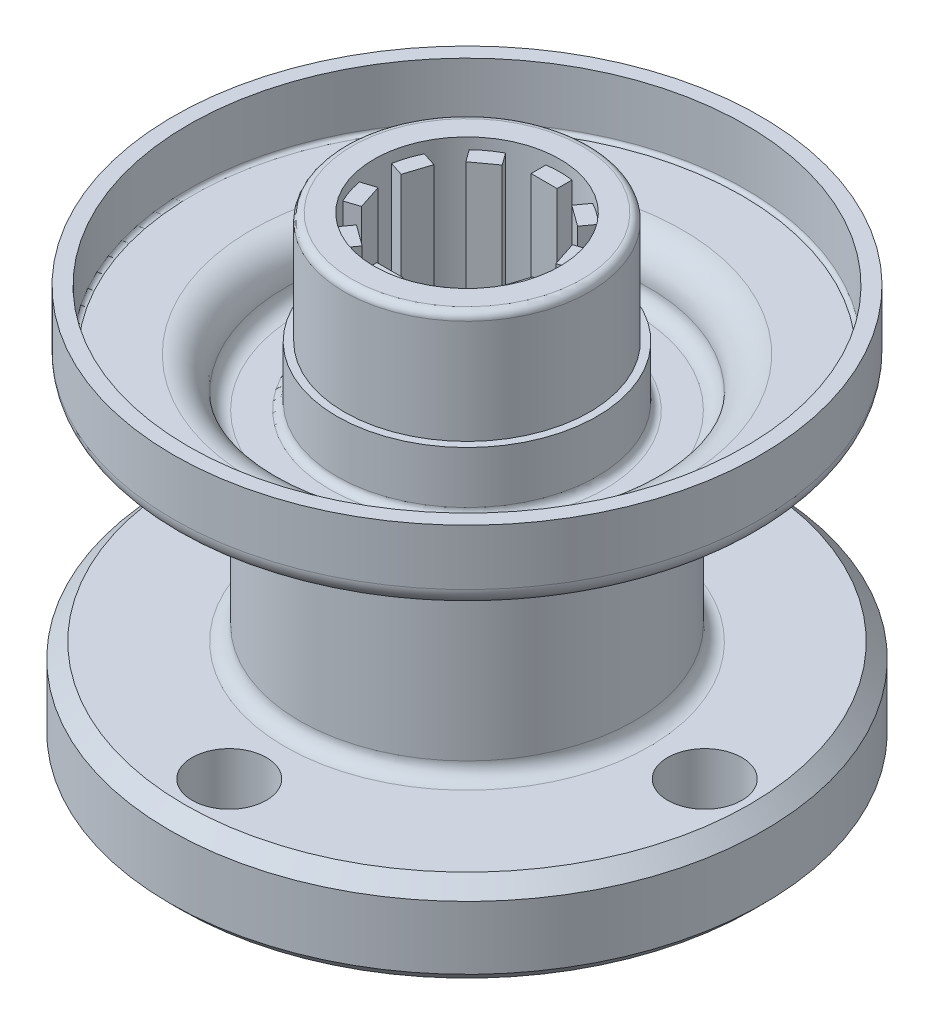
SolidWorks part; units mm, degrees
ref_plane "Front Plane" through (0, 0, 0) normal (0, 0, 1) x (1, 0, 0)
ref_plane "Top Plane" through (0, 0, 0) normal (0, 1, 0) x (1, 0, 0)
ref_plane "Right Plane" through (0, 0, 0) normal (1, 0, 0) x (0, 0, -1)
sketch "Sketch1" plane through (0, 0, 0) normal (0, 1, 0) x (1, 0, 0)
  circle A0 centre (0, 0) radius 40
  dimension "D1" = 80
extrude "Extrude1" add sketch "Sketch1" along normal blind 12
sketch "Sketch2" plane through (0, 12, 0) normal (0, 1, 0) x (1, 0, 0)
  circle A0 centre (0, 0) radius 22.5
  dimension "D1" = 45
extrude "Extrude2" add sketch "Sketch2" along normal blind 50
sketch "Sketch3" plane through (0, 0, 0) normal (0, 0, 1) x (1, 0, 0)
  line L0 (-29, 43.5) -> (-37, 43.5)
  line L1 (-39.5, 46) -> (-39.5, 53.5)
  line L2 (0, 37) -> (-22.5, 37)
  line L3 (0, 39) -> (-22.5, 39)
  line L4 (-29, 45.5) -> (-37, 45.5)
  line L5 (-37.5, 46) -> (-37.5, 53.5)
  line L6 (-39.5, 53.5) -> (-37.5, 53.5)
  line L7 (0, 39) -> (0, 37)
  arc A0 (-22.5, 37) -> (-26.5, 41) centre (-22.5, 41) cw
  arc A1 (-26.5, 41) -> (-29, 43.5) centre (-29, 41) ccw
  arc A2 (-37, 43.5) -> (-39.5, 46) centre (-37, 46) cw
  arc A3 (-22.5, 39) -> (-24.5, 41) centre (-22.5, 41) cw
  arc A4 (-24.5, 41) -> (-29, 45.5) centre (-29, 41) ccw
  arc A5 (-37, 45.5) -> (-37.5, 46) centre (-37, 46) cw
  dimension "D2" = 4
  dimension "D3" = 2.5
  dimension "D4" = 2.5
  dimension "D9" = 2.5
  dimension "D5" = 4
  dimension "D6" = 4
  dimension "D7" = 2.5
  dimension "D8" = 8
  dimension "D10" = 2.5
  dimension "D11" = 22.5
  dimension "D12" = 2.5
  dimension "D13" = 7.5
  dimension "D14" = 2
revolve "Revolve1" add sketch "Sketch3" angle 360 about L7
sketch "Sketch6" plane through (0, 0, 0) normal (0, -1, 0) x (1, 0, 0)
  circle A0 centre (0, 0) radius 25
  dimension "D1" = 50
extrude "Extrude5" cut sketch "Sketch6" against normal blind 6
sketch "Sketch7" plane through (0, 6, 0) normal (0, -1, 0) x (1, 0, 0)
  circle A0 centre (0, 0) radius 20
  dimension "D1" = 40
extrude "Extrude6" cut sketch "Sketch7" against normal blind 12
sketch "Sketch9" plane through (0, 0, 0) normal (0, -1, 0) x (1, 0, 0)
  circle A0 centre (0, 32) radius 5
  circle A1 centre (32, 0) radius 5
  circle A2 centre (0, -32) radius 5
  circle A3 centre (-32, 0) radius 5
  dimension "D1" = 10
  dimension "D2" = 32
extrude "Extrude8" cut sketch "Sketch9" against normal blind 20
sketch "Sketch10" plane through (0, 62, 0) normal (0, 1, 0) x (1, 0, 0)
  circle A0 centre (0, 0) radius 17.5
  circle A1 centre (0, 0) radius 22.5
  dimension "D1" = 35
  dimension "D2" = 45
extrude "Extrude9" cut sketch "Sketch10" against normal blind 23
sketch "Sketch12" plane through (0, 62, 0) normal (0, 1, 0) x (-1, 0, 0)
  line L0 (-4.6836, -9.4237) -> (-7.5152, -7.3665)
  line L1 (-5.8592, -11.0417) -> (-4.6836, -9.4237)
  line L2 (1.75, -12.3769) -> (1.75, -10.3769)
  line L3 (1.75, -10.3769) -> (-1.75, -10.3769)
  line L4 (-1.75, -12.3769) -> (-1.75, -10.3769)
  line L5 (-8.6907, -8.9845) -> (-7.5152, -7.3665)
  line L6 (-9.3282, -4.871) -> (-10.4098, -1.5423)
  line L7 (-11.2303, -5.489) -> (-9.3282, -4.871)
  line L8 (-12.3119, -2.1603) -> (-10.4098, -1.5423)
  line L9 (-10.4098, 1.5423) -> (-9.3282, 4.871)
  line L10 (-12.3119, 2.1603) -> (-10.4098, 1.5423)
  line L11 (-11.2303, 5.489) -> (-9.3282, 4.871)
  line L12 (-7.5152, 7.3665) -> (-4.6836, 9.4237)
  line L13 (-8.6907, 8.9845) -> (-7.5152, 7.3665)
  line L14 (-5.8592, 11.0417) -> (-4.6836, 9.4237)
  line L15 (-1.75, 10.3769) -> (1.75, 10.3769)
  line L16 (-1.75, 12.3769) -> (-1.75, 10.3769)
  line L17 (1.75, 12.3769) -> (1.75, 10.3769)
  line L18 (4.6836, 9.4237) -> (7.5152, 7.3665)
  line L19 (5.8592, 11.0417) -> (4.6836, 9.4237)
  line L20 (8.6907, 8.9845) -> (7.5152, 7.3665)
  line L21 (9.3282, 4.871) -> (10.4098, 1.5423)
  line L22 (11.2303, 5.489) -> (9.3282, 4.871)
  line L23 (12.3119, 2.1603) -> (10.4098, 1.5423)
  line L24 (10.4098, -1.5423) -> (9.3282, -4.871)
  line L25 (12.3119, -2.1603) -> (10.4098, -1.5423)
  line L26 (11.2303, -5.489) -> (9.3282, -4.871)
  line L27 (7.5152, -7.3665) -> (4.6836, -9.4237)
  line L28 (8.6907, -8.9845) -> (7.5152, -7.3665)
  line L29 (5.8592, -11.0417) -> (4.6836, -9.4237)
  arc A0 (1.75, -12.3769) -> (5.8592, -11.0417) centre (0, 0) ccw
  arc A1 (-5.8592, -11.0417) -> (-1.75, -12.3769) centre (0, 0) ccw
  arc A2 (-11.2303, -5.489) -> (-8.6907, -8.9845) centre (0, 0) ccw
  arc A3 (-12.3119, 2.1603) -> (-12.3119, -2.1603) centre (0, 0) ccw
  arc A4 (-8.6907, 8.9845) -> (-11.2303, 5.489) centre (0, 0) ccw
  arc A5 (5.8592, 11.0417) -> (1.75, 12.3769) centre (0, 0) ccw
  arc A6 (11.2303, 5.489) -> (8.6907, 8.9845) centre (0, 0) ccw
  arc A7 (12.3119, -2.1603) -> (12.3119, 2.1603) centre (0, 0) ccw
  arc A8 (8.6907, -8.9845) -> (11.2303, -5.489) centre (0, 0) ccw
  arc A9 (-1.75, 12.3769) -> (-5.8592, 11.0417) centre (0, 0) ccw
  point P3 (0, -12.5)
  dimension "D1" = 25
  dimension "D3" = 3.5
  dimension "D2" = 2
  dimension "D4" = 10.3769
extrude "Extrude12" cut sketch "Sketch12" against normal up to surface (44 mm away) up to face at (0, 18, -20)
sketch "Sketch14" plane through (0, 18, 0) normal (0, -1, 0) x (1, 0, 0)
  circle A0 centre (0, 0) radius 12.5
  dimension "D1" = 25
extrude "Extrude14" cut sketch "Sketch14" against normal blind 1.5
chamfer "Chamfer2" distance 2 angle 45 1 edges at (0, 12, 40)
chamfer "Chamfer3" distance 1.5 angle 45 1 edges at (0, 0, 40)
fillet "Fillet3" radius 0.5 1 edges at (0, 18, -12.5)
sketch "Sketch15" plane through (0, 62, 0) normal (0, 1, 0) x (1, 0, 0)
  circle A0 centre (0, 0) radius 16.5
  circle A1 centre (0, 0) radius 20
  dimension "D1" = 33
  dimension "D2" = 40
extrude "Extrude15" cut sketch "Sketch15" against normal blind 15
sketch "Sketch16" plane through (0, 62, 0) normal (0, 1, 0) x (-1, 0, 0)
  circle A0 centre (0, 0) radius 12.5
  dimension "D1" = 25
extrude "Extrude16" cut sketch "Sketch16" against normal blind 1.5
fillet "Fillet4" radius 1 1 edges at (0, 62, 16.5)
fillet "Fillet5" radius 2 1 edges at (0, 12, 22.5)
fillet "Fillet6" radius 1 1 edges at (0, 39, 17.5)
sketch "Sketch17" plane through (0, 0, 0) normal (0, 0, 1) x (1, 0, 0)
  line L0 (0, 0) -> (0, 47.06)
  line L1 (-20.5, 37) -> (-24.5, 37)
  line L2 (-20.5, 37) -> (-20.5, 36.5)
  line L3 (-20.5, 36.5) -> (-24.5, 36.5)
  line L4 (-24.5, 37) -> (-24.5, 36.5)
  line L5 (-20.5, 37) -> (-24.5, 36.5) construction
  line L6 (-20.5, 36.5) -> (-24.5, 37) construction
  point P0 (-22.5, 36.75)
  dimension "D1" = 22.5
  dimension "D2" = 4
  dimension "D3" = 0.5
  dimension "D4" = 36.75
revolve "Cut-Revolve1" cut sketch "Sketch17" angle 360 about L0
chamfer "Chamfer4" distance 2 angle 45 1 edges at (0, 36.5, -22.5)
